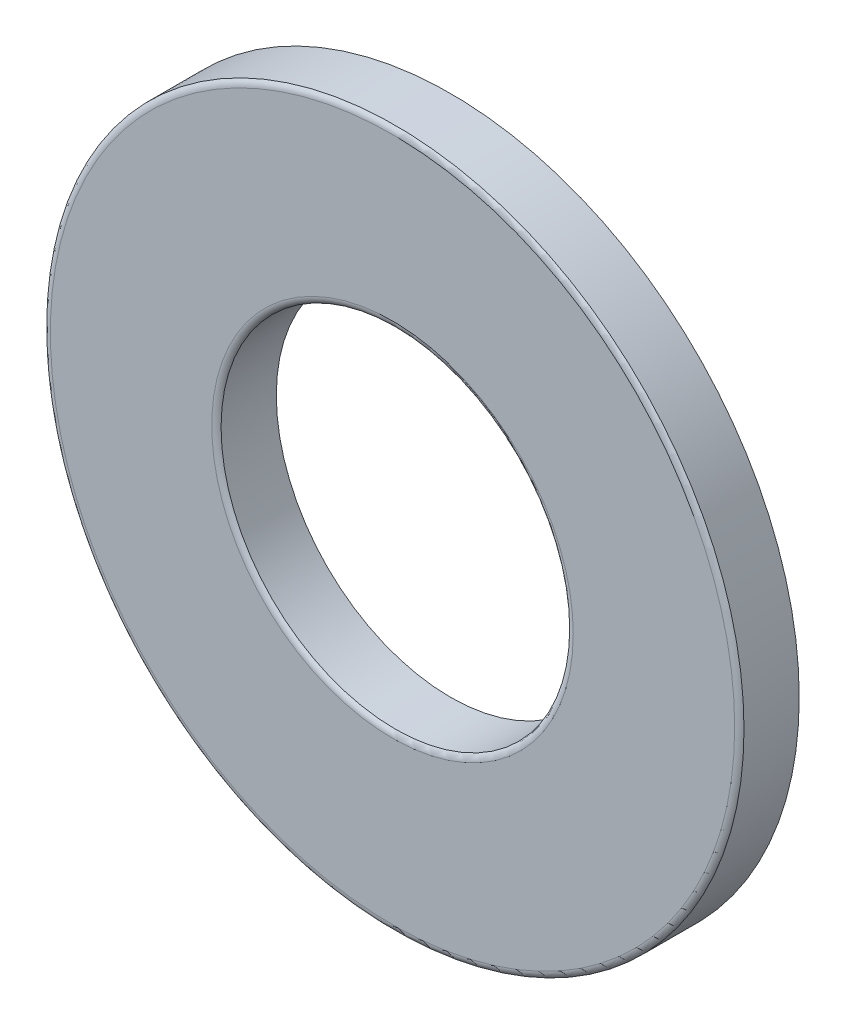
SolidWorks part; units mm, degrees
material "AISI 1020"
ref_plane "Front Plane" through (0, 0, 0) normal (0, 0, 1) x (1, 0, 0)
ref_plane "Top Plane" through (0, 0, 0) normal (0, 1, 0) x (1, 0, 0)
ref_plane "Right Plane" through (0, 0, 0) normal (1, 0, 0) x (0, 0, -1)
sketch "Sketch1" plane through (0, 0, 0) normal (0, 0, 1) x (1, 0, 0)
  circle A0 centre (0, 0) radius 19.05
  circle A1 centre (0, 0) radius 9.525
  point P4 (9.525, 0)
  dimension "ID" = 19.05
  dimension "OD" = 38.1
sketch "Sketch2" plane through (0, 0, 0) normal (1, 0, 0) x (0, 0, -1)
  line L0 (-0.7874, 19.05) -> (0.7874, 19.05)
  line L1 (0, 19.05) -> (0, 17.4752) construction
  point P2 (-0.8763, 19.05)
  point P3 (0, 19.05)
  point P4 (0.8763, 19.05)
  point P8 (-0.6985, 19.05)
  point P13 (0.6985, 19.05)
  dimension "Thickness Range" = 1.5748
  dimension "Thickness Range Max" = 1.7526
  dimension "Thickness Range Min" = 1.397
sketch "Sketch3" plane through (0, 0, 0) normal (0, 0, 1) x (1, 0, 0)
  circle A0 centre (0, 0) radius 9.525 construction
  circle A1 centre (0, 0) radius 19.05 construction
  circle A2 centre (0, 0) radius 9.525
  circle A3 centre (0, 0) radius 19.05
extrude "Boss-Extrude1" add sketch "Sketch3" along normal blind 3.175 from vertex at -0.7874 starting at point (0, 19.05, -0.7874)
chamfer "Chamfer1" distance 0.1575 angle 30 2 edges at (19.05, 0, 2.3876) (9.525, 0, 2.3876)
fillet "Fillet1" radius 0.4724 2 edges at (9.6159, 0, 2.3876) (18.9591, 0, 2.3876)
equation "\"D1@Fillet1\"=\"D1@Chamfer1\"*3"
equation "\"D1@Chamfer1\"=\"Thickness Range@Sketch2\"*.1"
